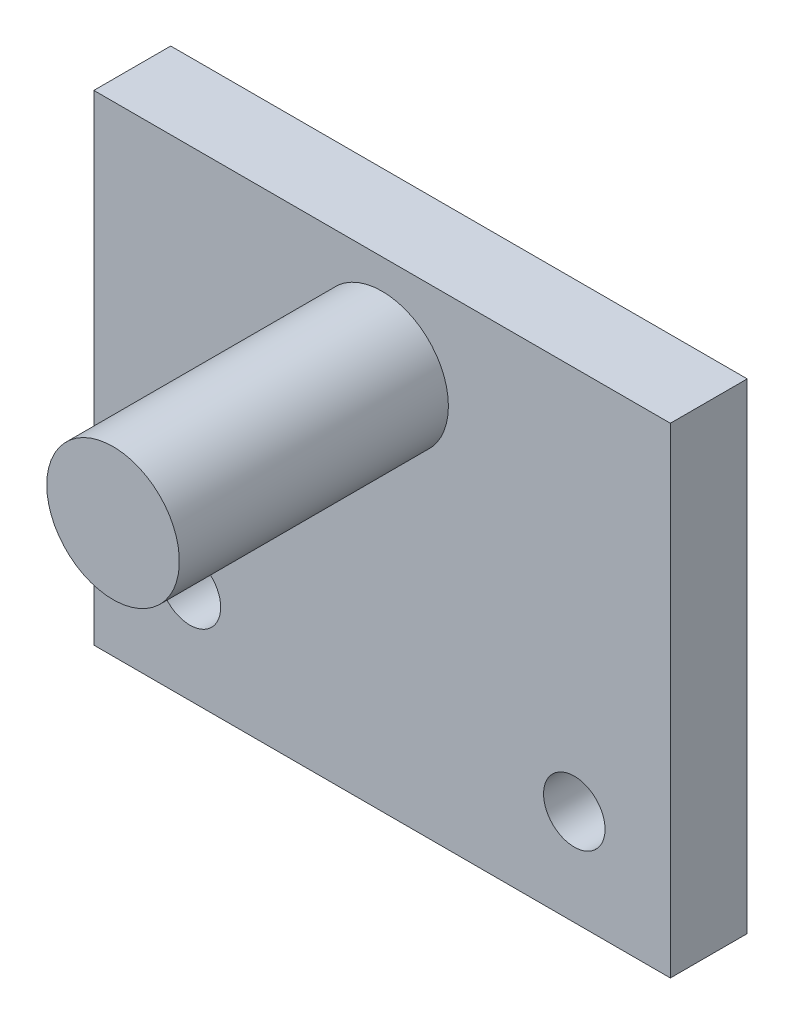
SolidWorks part; units mm, degrees
ref_plane "前视基准面" through (0, 0, 0) normal (0, 0, 1) x (1, 0, 0)
ref_plane "上视基准面" through (0, 0, 0) normal (0, 1, 0) x (1, 0, 0)
ref_plane "右视基准面" through (0, 0, 0) normal (1, 0, 0) x (0, 0, -1)
other "Configuration Table"
sketch "草图1" plane through (0, 0, 0) normal (0, 0, 1) x (1, 0, 0)
  line L0 (-30, 8.1585) -> (0, 8.1585) construction
  line L1 (-30, 28.1585) -> (0, 28.1585)
  line L2 (-30, 28.1585) -> (-30, 3.1585)
  line L3 (-30, 3.1585) -> (0, 3.1585)
  line L4 (0, 28.1585) -> (0, 3.1585)
  line L5 (-15, 28.1585) -> (-15, 3.1585) construction
  circle A0 centre (-5, 8.1585) radius 1.6
  circle A1 centre (-25, 8.1585) radius 1.6
  circle A2 centre (-15, 23.1585) radius 3.45
  point P12 (-15, 8.1585)
  dimension "D2" = 10
  dimension "D4" = 3.2
  dimension "D6" = 6.9
  dimension "D1" = 30
  dimension "D3" = 10
  dimension "D5" = 5
  dimension "D7" = 15
  dimension "D8" = 5
extrude "凸台-拉伸1" add sketch "草图1" along normal blind 4 contours A2 | L2 L1 L4 L3 | A1 | A0
sketch "草图2" plane through (0, 0, 4) normal (0, 0, 1) x (1, 0, 0)
  circle A0 centre (-15, 23.1585) radius 3.45
  circle A1 centre (-15, 23.1585) radius 3.45 construction
extrude "凸台-拉伸2" add sketch "草图2" along normal blind 18 from surface starting at face at (-23.4, 8.1585, 0)
